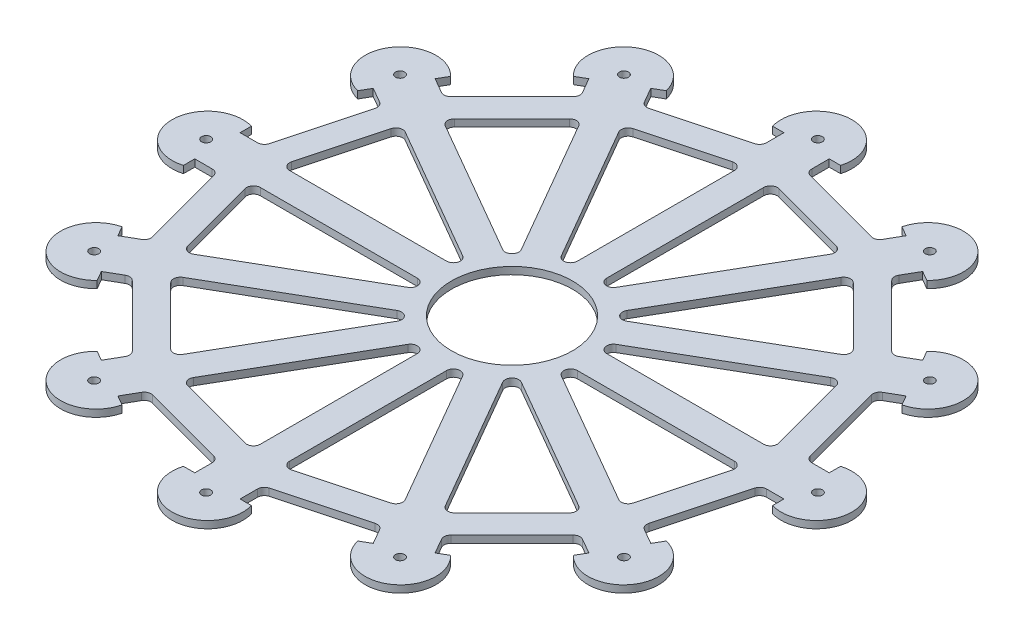
SolidWorks part; units mm, degrees
ref_plane "Front Plane" through (0, 0, 0) normal (0, 0, 1) x (1, 0, 0)
ref_plane "Top Plane" through (0, 0, 0) normal (0, 1, 0) x (1, 0, 0)
ref_plane "Right Plane" through (0, 0, 0) normal (1, 0, 0) x (0, 0, -1)
sketch "Sketch1" plane through (0, 0, 0) normal (0, 1, 0) x (1, 0, 0)
  line L0 (0, 0) -> (0, 150)
  line L1 (15, 130) -> (10, 130)
  line L2 (10, 130) -> (10, 120)
  line L3 (10, 120) -> (30.6699, 114.4615)
  line L4 (0, 0) -> (36.1011, 134.7312) construction
  line L5 (30.6699, 114.4615) -> (27.564, 102.8704)
  line L6 (27.564, 102.8704) -> (6.4705, 108.5224)
  line L7 (6.4705, 108.5224) -> (6.4705, 24.1481)
  line L8 (6.4705, 24.1481) -> (0, 0)
  arc A1 (0, 150) -> (15, 130) centre (0, 134.375) cw
  dimension "D3" = 5
  dimension "D1" = 15
  dimension "D2" = 15
  dimension "D4" = 10
  dimension "D5" = 20
  dimension "D6" = 150
  dimension "D7" = 25
  dimension "D8" = 12
extrude "Boss-Extrude1" add sketch "Sketch1" along normal blind 3.18
mirror "Mirror1" about plane through (30.6699, 3.18, -114.4615) normal (-0.9659, 0, -0.2588) of "Boss-Extrude1"
fillet "Fillet1" radius 3 5 edges at (6.4705, 1.59, -24.1481) (48.6576, 1.59, -97.2184) (6.4705, 1.59, -108.5224) (51.3397, 1.59, -108.923) (10, 1.59, -120)
ref_axis "Axis1" through (0, 3.18, 0) along (0, -1, 0)
pattern_circular "CirPattern27" count 12 over 360 about axis through (0, 3.18, 0) along (0, -1, 0) of bodies 102
combine bodies "Combine1" bodies to combine 110 111 112 113 102 103 104 105 106 107 108 109
sketch "Sketch3" plane through (0, 3.18, 0) normal (0, 1, 0) x (1, 0, 0)
  circle A0 centre (0, 0) radius 3.175
  dimension "D1" = 6.35
extrude "Cut-Extrude1" cut sketch "Sketch3" against normal through all
sketch "Sketch4" plane through (0, 3.18, 0) normal (0, 1, 0) x (1, 0, 0)
  line L0 (0, 0) -> (0, 15.97) construction
  circle A0 centre (0, 9.5) radius 1.35
  circle A1 centre (8.2272, 4.75) radius 1.35
  circle A2 centre (8.2272, -4.75) radius 1.35
  circle A3 centre (0, -9.5) radius 1.35
  circle A4 centre (-8.2272, -4.75) radius 1.35
  circle A5 centre (-8.2272, 4.75) radius 1.35
  point P19 (0, 0)
  dimension "D1" = 2.7
  dimension "9.5" = 9.5
  dimension "D2" = 6
extrude "Cut-Extrude2" cut sketch "Sketch4" against normal through all
sketch "Sketch5" plane through (0, 3.18, 0) normal (0, 1, 0) x (1, 0, 0)
  line L0 (0, 0) -> (0, 115.9813) construction
  circle A0 centre (0, 135) radius 2
  dimension "D1" = 4
  dimension "D2" = 135
extrude "Cut-Extrude3" cut sketch "Sketch5" against normal through all
pattern_circular "CirPattern28" count 12 every 30 about axis through (0, 3.18, 0) along (0, -1, 0) of "Cut-Extrude3"
sketch "Sketch6" plane through (0, 0, 0) normal (0, 1, 0) x (1, 0, 0)
  circle A0 centre (0, 0) radius 26.7211
extrude "Cut-Extrude5" cut sketch "Sketch6" against normal through all and the other way through all contours A0
